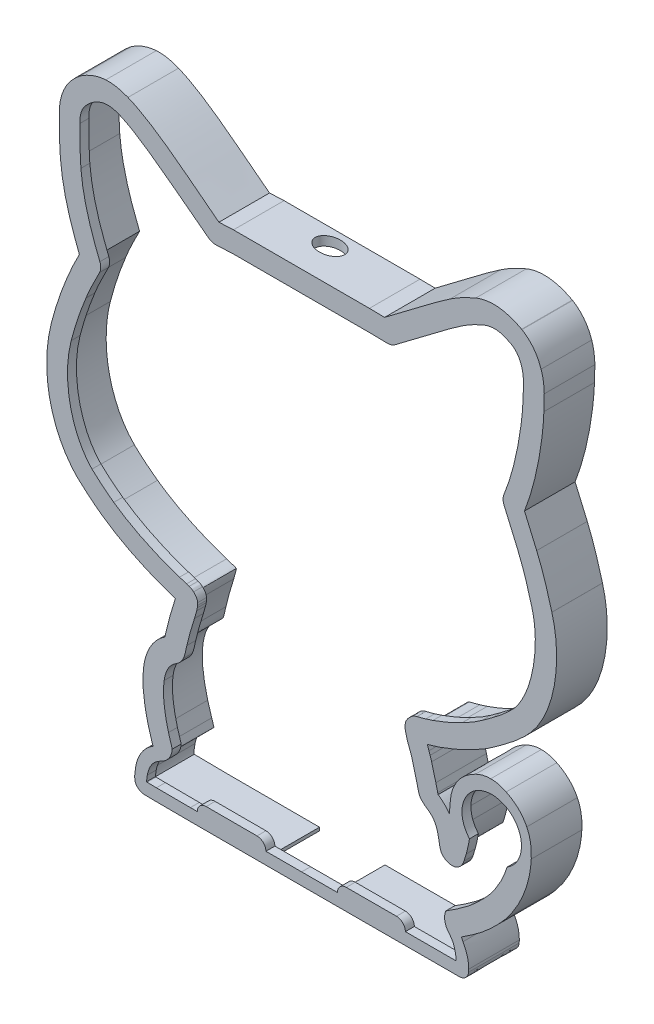
SolidWorks part; units mm, degrees
ref_plane "Front" through (0, 0, 0) normal (0, 0, 1) x (1, 0, 0)
ref_plane "Top" through (0, 0, 0) normal (0, 1, 0) x (1, 0, 0)
ref_plane "Right" through (0, 0, 0) normal (1, 0, 0) x (0, 0, -1)
sketch "Mech_Outlines_Dog" plane through (0, 0, 0) normal (0, 0, 1) x (1, 0, 0)
  line L1 (74.9398, 0.9126) -> (48.9706, 0.8869)
  line L7 (71.492, 32.5287) -> (70.2527, 32.1324)
  line L14 (63.42, 86.4697) -> (60.3508, 86.5232)
  line L15 (60.3508, 86.5232) -> (48.9353, 86.5232)
  line L16 (48.9353, 86.5232) -> (37.5273, 86.5232)
  line L17 (37.5273, 86.5232) -> (34.5339, 86.3884)
  line L22 (73.1431, 2.4109) -> (48.9672, 2.3716)
  line L27 (71.0247, 33.949) -> (69.8274, 33.5656)
  line L32 (63.3944, 84.986) -> (60.338, 85.0395)
  line L33 (60.338, 85.0395) -> (48.9354, 85.0395)
  line L34 (48.9354, 85.0395) -> (37.5613, 85.0395)
  line L35 (37.5613, 85.0395) -> (34.6011, 84.9061)
  line L40 (75.4762, -1.1182) -> (49.0458, -1.1447)
  line L42 (77.0346, 0.7654) -> (77.0108, 0.3114)
  line L48 (60.3548, 88.5576) -> (62.8985, 88.5136)
  line L51 (37.5165, 88.5576) -> (60.3548, 88.5576)
  line L53 (35.0717, 88.4472) -> (37.5165, 88.5576)
  line L56 (34.5113, 86.8831) -> (37.5166, 87.0182)
  line L57 (37.5166, 87.0182) -> (48.9356, 87.0182)
  line L58 (48.9356, 87.0182) -> (60.3546, 87.0182)
  line L59 (60.3546, 87.0182) -> (63.4286, 86.965)
  line L62 (70.4053, 31.6632) -> (71.6522, 32.0554)
  line L63 (75.4324, 0.8747) -> (75.3997, 0.419)
  line L64 (75.3997, 0.419) -> (48.9694, 0.3927)
  spline S0 degree 3 poles (16.1085, 97.6224) (15.1263, 97.5645) (14.0794, 97.2279) (12.9032, 96.4251) knots 0 0 0 0 1 1 1 1
  spline S1 degree 3 poles (12.9032, 96.4251) (10.8702, 94.8674) (10.2573, 93.2137) (10.2274, 91.1494) knots 0 0 0 0 1 1 1 1
  spline S2 degree 3 poles (10.2274, 91.1494) (10.1937, 88.8245) (10.2902, 85.9514) (10.4089, 84.5626) knots 0 0 0 0 1 1 1 1
  spline S3 degree 3 poles (10.4089, 84.5626) (10.8046, 79.9338) (12.2076, 75.8345) (13.7003, 72.1489) knots 0 0 0 0 1 1 1 1
  spline S4 degree 3 poles (13.7003, 72.1489) (13.7533, 72.018) (13.7479, 71.8706) (13.6854, 71.744) knots 0 0 0 0 1 1 1 1
  spline S5 degree 3 poles (13.6854, 71.744) (12.8695, 70.0922) (12.0156, 68.4848) (11.3692, 66.8103) knots 0 0 0 0 1 1 1 1
  spline S6 degree 3 poles (11.3692, 66.8103) (11.3675, 66.8062) (11.3657, 66.8022) (11.3638, 66.7981) knots 0 0 0 0 1 1 1 1
  spline S7 degree 3 poles (11.3638, 66.7981) (10.3632, 64.3951) (9.5104, 61.8412) (8.8174, 59.1813) knots 0 0 0 0 1 1 1 1
  spline S8 degree 3 poles (8.8174, 59.1813) (7.136, 52.6817) (8.6138, 44.9032) (12.7203, 40.814) knots 0 0 0 0 1 1 1 1
  spline S9 degree 3 poles (12.7203, 40.814) (13.8839, 39.7054) (15.1708, 38.6412) (16.5528, 37.6527) knots 0 0 0 0 1 1 1 1
  spline S10 degree 3 poles (16.5528, 37.6527) (19.588, 35.4818) (23.8433, 33.4143) (28.0129, 32.0933) knots 0 0 0 0 1 1 1 1
  spline S11 degree 3 poles (28.0129, 32.0933) (28.4457, 31.9562) (28.8478, 31.8228) (29.152, 31.7174) knots 0 0 0 0 1 1 1 1
  spline S12 degree 3 poles (29.152, 31.7174) (29.3041, 31.6647) (29.4314, 31.6193) (29.5293, 31.582) knots 0 0 0 0 1 1 1 1
  spline S13 degree 3 poles (29.5293, 31.582) (29.6997, 31.528) (29.7592, 31.4685) (29.8367, 31.4215) knots 0 0 0 0 1 1 1 1
  spline S14 degree 3 poles (29.8367, 31.4215) (30.0145, 31.2642) (29.9977, 31.1577) (30.0053, 31.0998) knots 0 0 0 0 1 1 1 1
  spline S15 degree 3 poles (30.0053, 31.0998) (30.013, 31.0418) (30.011, 31.008) (30.0094, 30.9765) knots 0 0 0 0 1 1 1 1
  spline S16 degree 3 poles (30.0094, 30.9765) (30.0062, 30.9135) (29.9984, 30.8639) (29.9884, 30.8065) knots 0 0 0 0 1 1 1 1
  spline S17 degree 3 poles (29.9884, 30.8065) (29.9685, 30.6918) (29.938, 30.5555) (29.897, 30.3921) knots 0 0 0 0 1 1 1 1
  spline S18 degree 3 poles (29.897, 30.3921) (29.815, 30.0653) (29.6927, 29.6377) (29.5475, 29.1758) knots 0 0 0 0 1 1 1 1
  spline S19 degree 3 poles (29.5475, 29.1758) (28.8677, 27.0124) (28.5655, 25.9343) (28.2351, 24.4934) knots 0 0 0 0 1 1 1 1
  spline S20 degree 3 poles (28.2351, 24.4934) (27.9956, 23.449) (27.9088, 22.9752) (27.7373, 22.5937) knots 0 0 0 0 1 1 1 1
  spline S21 degree 3 poles (27.7373, 22.5937) (27.6515, 22.403) (27.5225, 22.233) (27.3845, 22.1142) knots 0 0 0 0 1 1 1 1
  spline S22 degree 3 poles (27.3845, 22.1142) (27.2464, 21.9955) (27.1173, 21.9196) (26.9591, 21.8122) knots 0 0 0 0 1 1 1 1
  spline S23 degree 3 poles (26.9591, 21.8122) (25.5697, 20.8686) (24.7237, 19.4316) (24.4067, 17.4) knots 0 0 0 0 1 1 1 1
  spline S24 degree 3 poles (24.4067, 17.4) (24.0896, 15.3685) (24.3311, 12.7525) (25.1692, 9.5949) knots 0 0 0 0 1 1 1 1
  spline S25 degree 3 poles (25.1692, 9.5949) (25.3317, 8.9826) (25.6352, 7.9761) (25.8316, 7.3959) knots 0 0 0 0 1 1 1 1
  spline S26 degree 3 poles (25.8316, 7.3959) (25.9342, 7.0925) (26.0276, 6.8033) (26.0964, 6.5765) knots 0 0 0 0 1 1 1 1
  spline S27 degree 3 poles (26.0964, 6.5765) (26.1307, 6.4631) (26.1585, 6.3654) (26.1797, 6.2859) knots 0 0 0 0 1 1 1 1
  spline S28 degree 3 poles (26.1797, 6.2859) (26.1902, 6.2462) (26.1992, 6.2118) (26.2067, 6.1769) knots 0 0 0 0 1 1 1 1
  spline S29 degree 3 poles (26.2067, 6.1769) (26.2143, 6.142) (26.2257, 6.1318) (26.2257, 6.0245) knots 0 0 0 0 1 1 1 1
  spline S30 degree 3 poles (26.2257, 6.0245) (26.2257, 5.8348) (26.1568, 5.7565) (26.1167, 5.7015) knots 0 0 0 0 1 1 1 1
  spline S31 degree 3 poles (26.1167, 5.7015) (26.0766, 5.6465) (26.0428, 5.6144) (26.0097, 5.5843) knots 0 0 0 0 1 1 1 1
  spline S32 degree 3 poles (26.0097, 5.5843) (25.9433, 5.5242) (25.878, 5.4775) (25.8031, 5.4286) knots 0 0 0 0 1 1 1 1
  spline S33 degree 3 poles (25.8031, 5.4286) (25.6534, 5.3307) (25.4697, 5.2302) (25.2654, 5.1346) knots 0 0 0 0 1 1 1 1
  spline S34 degree 3 poles (25.2654, 5.1346) (24.0959, 4.5874) (23.3401, 3.5522) (23.0427, 1.9977) knots 0 0 0 0 1 1 1 1
  spline S35 degree 3 poles (23.0427, 1.9977) (22.964, 1.5861) (22.9165, 1.2157) (22.8985, 0.9548) knots 0 0 0 0 1 1 1 1
  spline S36 degree 3 poles (22.8985, 0.9548) (22.8982, 0.9505) (22.8987, 0.9495) (22.8985, 0.9453) knots 0 0 0 0 1 1 1 1
  spline S37 degree 3 poles (22.8985, 0.9453) (22.9412, 0.9442) (22.9602, 0.9428) (23.0095, 0.9418) knots 0 0 0 0 1 1 1 1
  spline S38 degree 3 poles (23.0095, 0.9418) (23.3672, 0.9341) (23.895, 0.9269) (24.5719, 0.9208) knots 0 0 0 0 1 1 1 1
  spline S39 degree 3 poles (24.5719, 0.9208) (25.9256, 0.9085) (27.8776, 0.8993) (30.281, 0.893) knots 0 0 0 0 1 1 1 1
  spline S40 degree 3 poles (30.281, 0.893) (35.0878, 0.8804) (41.7026, 0.8797) (48.9706, 0.8869) knots 0 0 0 0 1 1 1 1
  spline S41 degree 3 poles (74.9398, 0.9126) (74.9724, 1.3839) (74.669, 2.8108) (74.3757, 3.392) knots 0 0 0 0 1 1 1 1
  spline S42 degree 3 poles (74.3757, 3.392) (74.2334, 3.6739) (73.9, 4.1595) (73.7316, 4.3421) knots 0 0 0 0 1 1 1 1
  spline S43 degree 3 poles (73.7316, 4.3421) (73.6085, 4.4757) (73.4981, 4.6071) (73.4106, 4.7234) knots 0 0 0 0 1 1 1 1
  spline S44 degree 3 poles (73.4106, 4.7234) (73.3669, 4.7816) (73.329, 4.8348) (73.2941, 4.8927) knots 0 0 0 0 1 1 1 1
  spline S45 degree 3 poles (73.2941, 4.8927) (73.2767, 4.9217) (73.2598, 4.9511) (73.2413, 4.993) knots 0 0 0 0 1 1 1 1
  spline S46 degree 3 poles (73.2413, 4.993) (73.2228, 5.0349) (73.1905, 5.076) (73.1905, 5.2219) knots 0 0 0 0 1 1 1 1
  spline S47 degree 3 poles (73.1905, 5.2219) (73.1905, 5.5363) (73.3056, 5.5597) (73.3578, 5.616) knots 0 0 0 0 1 1 1 1
  spline S48 degree 3 poles (73.3578, 5.616) (73.41, 5.6724) (73.4583, 5.7124) (73.5122, 5.7542) knots 0 0 0 0 1 1 1 1
  spline S49 degree 3 poles (73.5122, 5.7542) (73.6199, 5.8378) (73.7464, 5.9196) (73.8881, 5.998) knots 0 0 0 0 1 1 1 1
  spline S50 degree 3 poles (73.8881, 5.998) (74.7385, 6.4683) (76.9394, 7.9781) (77.9813, 8.8146) knots 0 0 0 0 1 1 1 1
  spline S51 degree 3 poles (77.9813, 8.8146) (79.226, 9.8139) (80.8168, 11.3707) (81.637, 12.3836) knots 0 0 0 0 1 1 1 1
  spline S52 degree 3 poles (81.637, 12.3836) (84.0319, 15.3411) (85.3661, 18.6885) (85.5378, 22.1256) knots 0 0 0 0 1 1 1 1
  spline S53 degree 3 poles (85.5378, 22.1256) (85.6136, 23.643) (85.4812, 24.4092) (84.9811, 25.4434) knots 0 0 0 0 1 1 1 1
  spline S54 degree 3 poles (84.9811, 25.4434) (84.4438, 26.5544) (83.7351, 27.2385) (82.4747, 27.8394) knots 0 0 0 0 1 1 1 1
  spline S55 degree 3 poles (82.4747, 27.8394) (81.5208, 28.2943) (81.637, 28.2688) (80.7593, 28.2688) knots 0 0 0 0 1 1 1 1
  spline S56 degree 3 poles (80.7593, 28.2688) (79.8855, 28.2688) (79.9954, 28.293) (79.0797, 27.8543) knots 0 0 0 0 1 1 1 1
  spline S57 degree 3 poles (79.0797, 27.8543) (77.5705, 27.1313) (76.7543, 26.2458) (76.259, 24.8217) knots 0 0 0 0 1 1 1 1
  spline S58 degree 3 poles (76.259, 24.8217) (76.0847, 24.3204) (76.007, 23.8462) (75.938, 22.7575) knots 0 0 0 0 1 1 1 1
  spline S59 degree 3 poles (75.938, 22.7575) (75.8864, 21.9425) (75.7936, 20.8688) (75.7267, 20.3289) knots 0 0 0 0 1 1 1 1
  spline S60 degree 3 poles (75.7267, 20.3289) (75.6352, 19.5905) (75.4028, 18.5493) (75.1701, 17.6863) knots 0 0 0 0 1 1 1 1
  spline S61 degree 3 poles (75.1701, 17.6863) (75.0537, 17.2549) (74.9391, 16.8726) (74.8348, 16.5885) knots 0 0 0 0 1 1 1 1
  spline S62 degree 3 poles (74.8348, 16.5885) (74.7827, 16.4465) (74.7375, 16.3338) (74.6736, 16.2215) knots 0 0 0 0 1 1 1 1
  spline S63 degree 3 poles (74.6736, 16.2215) (74.6417, 16.1654) (74.6178, 16.1084) (74.5125, 16.0204) knots 0 0 0 0 1 1 1 1
  spline S64 degree 3 poles (74.5125, 16.0204) (74.4598, 15.9763) (74.3749, 15.9137) (74.226, 15.8984) knots 0 0 0 0 1 1 1 1
  spline S65 degree 3 poles (74.226, 15.8984) (74.0771, 15.8832) (73.8945, 15.9611) (73.8088, 16.0468) knots 0 0 0 0 1 1 1 1
  spline S66 degree 3 poles (73.8088, 16.0468) (73.6952, 16.1604) (73.7087, 16.1881) (73.6971, 16.2161) knots 0 0 0 0 1 1 1 1
  spline S67 degree 3 poles (73.6971, 16.2161) (73.6855, 16.244) (73.6793, 16.2621) (73.674, 16.2791) knots 0 0 0 0 1 1 1 1
  spline S68 degree 3 poles (73.674, 16.2791) (73.6635, 16.313) (73.6564, 16.3423) (73.6483, 16.3759) knots 0 0 0 0 1 1 1 1
  spline S69 degree 3 poles (73.6483, 16.3759) (73.6321, 16.4431) (73.6147, 16.5243) (73.5955, 16.6217) knots 0 0 0 0 1 1 1 1
  spline S70 degree 3 poles (73.5955, 16.6217) (73.5571, 16.8166) (73.512, 17.0723) (73.4675, 17.3484) knots 0 0 0 0 1 1 1 1
  spline S71 degree 3 poles (73.4675, 17.3484) (73.116, 19.5286) (72.2864, 20.9205) (70.8513, 21.8493) knots 0 0 0 0 1 1 1 1
  spline S72 degree 3 poles (70.8513, 21.8493) (70.681, 21.9596) (70.5241, 22.0799) (70.3929, 22.1988) knots 0 0 0 0 1 1 1 1
  spline S73 degree 3 poles (70.3929, 22.1988) (70.3273, 22.2582) (70.2681, 22.3165) (70.2134, 22.3816) knots 0 0 0 0 1 1 1 1
  spline S74 degree 3 poles (70.2134, 22.3816) (70.1586, 22.4467) (70.1012, 22.4987) (70.0536, 22.662) knots 0 0 0 0 1 1 1 1
  spline S75 degree 3 poles (70.0536, 22.662) (70.022, 22.77) (69.9713, 22.98) (69.8836, 23.3358) knots 0 0 0 0 1 1 1 1
  spline S76 degree 3 poles (69.8836, 23.3358) (69.7959, 23.6916) (69.6827, 24.1554) (69.5653, 24.6422) knots 0 0 0 0 1 1 1 1
  spline S77 degree 3 poles (69.5653, 24.6422) (69.3325, 25.607) (69.0226, 26.7879) (68.8928, 27.2143) knots 0 0 0 0 1 1 1 1
  spline S78 degree 3 poles (68.8928, 27.2143) (68.829, 27.4238) (68.7314, 27.6944) (68.6449, 27.943) knots 0 0 0 0 1 1 1 1
  spline S79 degree 3 poles (68.6449, 27.943) (68.4728, 28.6982) (68.1277, 29.2538) (67.902, 30.1603) knots 0 0 0 0 1 1 1 1
  spline S80 degree 3 poles (67.902, 30.1603) (67.8356, 30.4354) (67.788, 30.6996) (67.8519, 30.9947) knots 0 0 0 0 1 1 1 1
  spline S81 degree 3 poles (67.8519, 30.9947) (67.9158, 31.2897) (68.2169, 31.6162) (68.5562, 31.6746) knots 0 0 0 0 1 1 1 1
  spline S82 degree 3 poles (68.5562, 31.6746) (68.7453, 31.7047) (69.5821, 31.9215) (70.2527, 32.1324) knots 0 0 0 0 1 1 1 1
  spline S83 degree 3 poles (71.492, 32.5287) (73.2584, 33.1478) (74.9712, 33.8823) (76.6363, 34.7642) knots 0 0 0 0 1 1 1 1
  spline S84 degree 3 poles (76.6363, 34.7642) (76.639, 34.7656) (76.6421, 34.767) (76.6451, 34.7683) knots 0 0 0 0 1 1 1 1
  spline S85 degree 3 poles (76.6451, 34.7683) (78.05, 35.4763) (79.1164, 36.1165) (80.1477, 36.8684) knots 0 0 0 0 1 1 1 1
  spline S86 degree 3 poles (80.1477, 36.8684) (80.5017, 37.1265) (81.2678, 37.6841) (81.8523, 38.1077) knots 0 0 0 0 1 1 1 1
  spline S87 degree 3 poles (81.8523, 38.1077) (82.9542, 38.9064) (84.0321, 39.8115) (85.0441, 40.7815) knots 0 0 0 0 1 1 1 1
  spline S88 degree 3 poles (85.0441, 40.7815) (89.4404, 44.9023) (90.6758, 53.4557) (89.0723, 59.1176) knots 0 0 0 0 1 1 1 1
  spline S89 degree 3 poles (89.0723, 59.1176) (89.0713, 59.121) (89.0706, 59.1243) (89.0695, 59.1277) knots 0 0 0 0 1 1 1 1
  spline S90 degree 3 poles (89.0695, 59.1277) (88.3821, 61.7674) (87.5422, 64.3151) (86.5996, 66.5786) knots 0 0 0 0 1 1 1 1
  spline S91 degree 3 poles (86.5996, 66.5786) (85.9445, 68.1619) (85.0951, 70.1031) (84.3316, 71.8319) knots 0 0 0 0 1 1 1 1
  spline S92 degree 3 poles (84.3316, 71.8319) (84.277, 71.9552) (84.2751, 72.0953) (84.3262, 72.22) knots 0 0 0 0 1 1 1 1
  spline S93 degree 3 poles (84.3262, 72.22) (86.2256, 76.8323) (87.4523, 83.2033) (87.6568, 88.2549) knots 0 0 0 0 1 1 1 1
  spline S94 degree 3 poles (87.6568, 88.2549) (87.6933, 89.156) (87.7129, 90.0068) (87.7164, 90.806) knots 0 0 0 0 1 1 1 1
  spline S95 degree 3 poles (87.7164, 90.806) (87.7165, 91.2801) (87.6649, 92.3563) (87.2904, 93.4831) knots 0 0 0 0 1 1 1 1
  spline S96 degree 3 poles (87.2904, 93.4831) (86.9162, 94.609) (86.2349, 95.7695) (84.9729, 96.5191) knots 0 0 0 0 1 1 1 1
  spline S97 degree 3 poles (84.9729, 96.5191) (83.6571, 97.2286) (81.5853, 98.1604) (79.0153, 97.1117) knots 0 0 0 0 1 1 1 1
  spline S98 degree 3 poles (79.0153, 97.1117) (77.7563, 96.598) (76.3931, 95.8948) (75.0467, 94.9927) knots 0 0 0 0 1 1 1 1
  spline S99 degree 3 poles (75.0467, 94.9927) (71.9886, 92.9435) (67.928, 89.6189) (63.7193, 86.5645) knots 0 0 0 0 1 1 1 1
  spline S100 degree 3 poles (63.7193, 86.5645) (63.6325, 86.5012) (63.5274, 86.4679) (63.42, 86.4697) knots 0 0 0 0 1 1 1 1
  spline S101 degree 3 poles (34.5339, 86.3884) (34.4203, 86.3833) (34.3084, 86.4175) (34.217, 86.4853) knots 0 0 0 0 1 1 1 1
  spline S102 degree 3 poles (34.217, 86.4853) (29.3204, 90.1096) (23.1108, 95.3799) (18.9569, 97.08) knots 0 0 0 0 1 1 1 1
  spline S103 degree 3 poles (18.9569, 97.08) (18.0268, 97.4561) (17.0933, 97.6805) (16.1085, 97.6224) knots 0 0 0 0 1 1 1 1
  spline S104 degree 3 poles (16.1938, 96.1413) (15.4989, 96.1004) (14.7441, 95.8759) (13.7687, 95.2169) knots 0 0 0 0 1 1 1 1
  spline S105 degree 3 poles (13.7687, 95.2169) (12.0783, 93.9098) (11.7344, 92.871) (11.7092, 91.1291) knots 0 0 0 0 1 1 1 1
  spline S106 degree 3 poles (11.7092, 91.1291) (11.6763, 88.8622) (11.776, 85.976) (11.8859, 84.69) knots 0 0 0 0 1 1 1 1
  spline S107 degree 3 poles (11.8859, 84.69) (12.2626, 80.2837) (13.6038, 76.3379) (15.0744, 72.707) knots 0 0 0 0 1 1 1 1
  spline S108 degree 3 poles (15.0744, 72.707) (15.2863, 72.1834) (15.2643, 71.5942) (15.0141, 71.0877) knots 0 0 0 0 1 1 1 1
  spline S109 degree 3 poles (15.0141, 71.0877) (14.185, 69.4091) (13.3549, 67.84) (12.7515, 66.2767) knots 0 0 0 0 1 1 1 1
  spline S110 degree 3 poles (12.7515, 66.2767) (12.7453, 66.2605) (12.739, 66.2445) (12.7325, 66.2286) knots 0 0 0 0 1 1 1 1
  spline S111 degree 3 poles (12.7325, 66.2286) (11.7606, 63.8947) (10.9288, 61.4063) (10.2525, 58.8108) knots 0 0 0 0 1 1 1 1
  spline S112 degree 3 poles (10.2525, 58.8108) (8.6952, 52.7918) (10.1873, 45.4432) (13.7558, 41.878) knots 0 0 0 0 1 1 1 1
  spline S113 degree 3 poles (13.7558, 41.878) (14.8637, 40.8235) (16.0922, 39.8065) (17.4142, 38.8609) knots 0 0 0 0 1 1 1 1
  spline S114 degree 3 poles (17.4142, 38.8609) (20.2797, 36.8114) (24.4364, 34.7832) (28.4592, 33.5087) knots 0 0 0 0 1 1 1 1
  spline S115 degree 3 poles (28.4592, 33.5087) (28.903, 33.3681) (29.3143, 33.2323) (29.6362, 33.1207) knots 0 0 0 0 1 1 1 1
  spline S116 degree 3 poles (29.6362, 33.1207) (29.7972, 33.0649) (29.9337, 33.016) (30.0568, 32.969) knots 0 0 0 0 1 1 1 1
  spline S117 degree 3 poles (30.0568, 32.969) (30.6405, 32.7016) (30.339, 32.9545) (30.818, 32.5342) knots 0 0 0 0 1 1 1 1
  spline S118 degree 3 poles (30.818, 32.5342) (31.5202, 31.9131) (31.4475, 31.5028) (31.4749, 31.2955) knots 0 0 0 0 1 1 1 1
  spline S119 degree 3 poles (31.4749, 31.2955) (31.5024, 31.0883) (31.4942, 30.9868) (31.4898, 30.9014) knots 0 0 0 0 1 1 1 1
  spline S120 degree 3 poles (31.4898, 30.9014) (31.4811, 30.7305) (31.4648, 30.6433) (31.4492, 30.5533) knots 0 0 0 0 1 1 1 1
  spline S121 degree 3 poles (31.4492, 30.5533) (31.4179, 30.3732) (31.3803, 30.2159) (31.3341, 30.0318) knots 0 0 0 0 1 1 1 1
  spline S122 degree 3 poles (31.3341, 30.0318) (31.2416, 29.6635) (31.1141, 29.2167) (30.9616, 28.7315) knots 0 0 0 0 1 1 1 1
  spline S123 degree 3 poles (30.9616, 28.7315) (30.2864, 26.583) (30.002, 25.5679) (29.6796, 24.1622) knots 0 0 0 0 1 1 1 1
  spline S124 degree 3 poles (29.6796, 24.1622) (29.4419, 23.1257) (29.4009, 22.6792) (29.0891, 21.9856) knots 0 0 0 0 1 1 1 1
  spline S125 degree 3 poles (29.0891, 21.9856) (28.9331, 21.6388) (28.6202, 21.2223) (28.3502, 20.9901) knots 0 0 0 0 1 1 1 1
  spline S126 degree 3 poles (28.3502, 20.9901) (28.0802, 20.7578) (27.9259, 20.6757) (27.7915, 20.5844) knots 0 0 0 0 1 1 1 1
  spline S127 degree 3 poles (27.7915, 20.5844) (26.7593, 19.8835) (26.1415, 18.9015) (25.8715, 17.1718) knots 0 0 0 0 1 1 1 1
  spline S128 degree 3 poles (25.8715, 17.1718) (25.6015, 15.4421) (25.7971, 13.0078) (26.6016, 9.9769) knots 0 0 0 0 1 1 1 1
  spline S129 degree 3 poles (26.6016, 9.9769) (26.7505, 9.4157) (27.0568, 8.4004) (27.2355, 7.8727) knots 0 0 0 0 1 1 1 1
  spline S130 degree 3 poles (27.2355, 7.8727) (27.3428, 7.5557) (27.4394, 7.2555) (27.5145, 7.0079) knots 0 0 0 0 1 1 1 1
  spline S131 degree 3 poles (27.5145, 7.0079) (27.552, 6.8841) (27.5835, 6.7751) (27.612, 6.6679) knots 0 0 0 0 1 1 1 1
  spline S132 degree 3 poles (27.612, 6.6679) (27.6262, 6.6143) (27.6399, 6.5627) (27.6553, 6.4912) knots 0 0 0 0 1 1 1 1
  spline S133 degree 3 poles (27.6553, 6.4912) (27.6708, 6.4196) (27.7075, 6.4282) (27.7075, 6.0252) knots 0 0 0 0 1 1 1 1
  spline S134 degree 3 poles (27.7075, 6.0252) (27.7075, 5.2923) (27.4472, 5.0106) (27.314, 4.8279) knots 0 0 0 0 1 1 1 1
  spline S135 degree 3 poles (27.314, 4.8279) (27.1808, 4.6452) (27.0851, 4.5581) (27.0038, 4.4845) knots 0 0 0 0 1 1 1 1
  spline S136 degree 3 poles (27.0038, 4.4845) (26.8414, 4.3374) (26.7289, 4.2629) (26.6131, 4.1872) knots 0 0 0 0 1 1 1 1
  spline S137 degree 3 poles (26.6131, 4.1872) (26.3815, 4.0358) (26.1526, 3.9128) (25.8925, 3.791) knots 0 0 0 0 1 1 1 1
  spline S138 degree 3 poles (25.8925, 3.791) (25.3519, 3.538) (25.011, 3.0738) (24.7561, 2.4054) knots 0 0 0 0 1 1 1 1
  spline S139 degree 3 poles (24.7561, 2.4054) (26.098, 2.3937) (27.954, 2.3844) (30.283, 2.3783) knots 0 0 0 0 1 1 1 1
  spline S140 degree 3 poles (30.283, 2.3783) (35.0865, 2.3658) (41.7003, 2.3644) (48.9672, 2.3716) knots 0 0 0 0 1 1 1 1
  spline S141 degree 3 poles (73.1431, 2.4109) (73.1124, 2.5325) (73.0842, 2.6997) (73.0645, 2.7386) knots 0 0 0 0 1 1 1 1
  spline S142 degree 3 poles (73.0645, 2.7386) (72.8449, 3.1433) (72.4981, 3.5205) (72.2383, 3.8473) knots 0 0 0 0 1 1 1 1
  spline S143 degree 3 poles (72.2383, 3.8473) (72.1747, 3.9319) (72.1144, 4.0144) (72.0372, 4.1425) knots 0 0 0 0 1 1 1 1
  spline S144 degree 3 poles (72.0372, 4.1425) (71.9985, 4.2066) (71.9552, 4.279) (71.8977, 4.4094) knots 0 0 0 0 1 1 1 1
  spline S145 degree 3 poles (71.8977, 4.4094) (71.8401, 4.5398) (71.7209, 4.6745) (71.7209, 5.2376) knots 0 0 0 0 1 1 1 1
  spline S146 degree 3 poles (71.7209, 5.2376) (71.7209, 6.4544) (72.1416, 6.4876) (72.283, 6.6402) knots 0 0 0 0 1 1 1 1
  spline S147 degree 3 poles (72.283, 6.6402) (72.4244, 6.7928) (72.5209, 6.869) (72.6162, 6.9429) knots 0 0 0 0 1 1 1 1
  spline S148 degree 3 poles (72.6162, 6.9429) (72.8068, 7.0908) (72.9824, 7.201) (73.1844, 7.3127) knots 0 0 0 0 1 1 1 1
  spline S149 degree 3 poles (73.1844, 7.3127) (73.8246, 7.6667) (76.1327, 9.2382) (77.0663, 9.9878) knots 0 0 0 0 1 1 1 1
  spline S150 degree 3 poles (77.0663, 9.9878) (78.2095, 10.9055) (79.7957, 12.4662) (80.4979, 13.3333) knots 0 0 0 0 1 1 1 1
  spline S151 degree 3 poles (80.4979, 13.3333) (82.7172, 16.074) (83.9146, 19.1142) (84.0696, 22.2159) knots 0 0 0 0 1 1 1 1
  spline S152 degree 3 poles (84.0696, 22.2159) (84.1391, 23.608) (84.0692, 23.9653) (83.6592, 24.8131) knots 0 0 0 0 1 1 1 1
  spline S153 degree 3 poles (83.6592, 24.8131) (83.2508, 25.6575) (82.8926, 26.0183) (81.8496, 26.5156) knots 0 0 0 0 1 1 1 1
  spline S154 degree 3 poles (81.8496, 26.5156) (81.404, 26.7167) (81.6277, 26.8014) (80.7735, 26.8014) knots 0 0 0 0 1 1 1 1
  spline S155 degree 3 poles (80.7735, 26.8014) (79.9242, 26.8014) (80.2197, 26.7515) (79.7353, 26.5326) knots 0 0 0 0 1 1 1 1
  spline S156 degree 3 poles (79.7353, 26.5326) (78.4713, 25.9612) (78.0585, 25.4528) (77.6751, 24.3505) knots 0 0 0 0 1 1 1 1
  spline S157 degree 3 poles (77.6751, 24.3505) (77.5544, 24.0033) (77.4994, 23.7229) (77.4334, 22.6798) knots 0 0 0 0 1 1 1 1
  spline S158 degree 3 poles (77.4334, 22.6798) (77.3798, 21.8337) (77.2901, 20.778) (77.214, 20.1632) knots 0 0 0 0 1 1 1 1
  spline S159 degree 3 poles (77.214, 20.1632) (77.105, 19.2836) (76.865, 18.2328) (76.618, 17.3168) knots 0 0 0 0 1 1 1 1
  spline S160 degree 3 poles (76.618, 17.3168) (76.4945, 16.8587) (76.374, 16.4531) (76.2421, 16.0937) knots 0 0 0 0 1 1 1 1
  spline S161 degree 3 poles (76.2421, 16.0937) (76.1762, 15.914) (76.1262, 15.7639) (75.9787, 15.5045) knots 0 0 0 0 1 1 1 1
  spline S162 degree 3 poles (75.9787, 15.5045) (75.9049, 15.3748) (75.8576, 15.2148) (75.4789, 14.8984) knots 0 0 0 0 1 1 1 1
  spline S163 degree 3 poles (75.4789, 14.8984) (75.2895, 14.7402) (74.9692, 14.4978) (74.3919, 14.4385) knots 0 0 0 0 1 1 1 1
  spline S164 degree 3 poles (74.3919, 14.4385) (73.8146, 14.3792) (73.1017, 14.6865) (72.774, 15.0142) knots 0 0 0 0 1 1 1 1
  spline S165 degree 3 poles (72.774, 15.0142) (72.324, 15.4641) (72.381, 15.5658) (72.3406, 15.663) knots 0 0 0 0 1 1 1 1
  spline S166 degree 3 poles (72.3406, 15.663) (72.3001, 15.7602) (72.2851, 15.8107) (72.2715, 15.8546) knots 0 0 0 0 1 1 1 1
  spline S167 degree 3 poles (72.2715, 15.8546) (72.2442, 15.9424) (72.2318, 15.9928) (72.2194, 16.0443) knots 0 0 0 0 1 1 1 1
  spline S168 degree 3 poles (72.2194, 16.0443) (72.1945, 16.1472) (72.1753, 16.2414) (72.1537, 16.351) knots 0 0 0 0 1 1 1 1
  spline S169 degree 3 poles (72.1537, 16.351) (72.1104, 16.5703) (72.0631, 16.8376) (72.0162, 17.1285) knots 0 0 0 0 1 1 1 1
  spline S170 degree 3 poles (72.0162, 17.1285) (71.7093, 19.0315) (71.1304, 19.9262) (70.059, 20.6196) knots 0 0 0 0 1 1 1 1
  spline S171 degree 3 poles (70.059, 20.6196) (69.8204, 20.7741) (69.6132, 20.9315) (69.4102, 21.1154) knots 0 0 0 0 1 1 1 1
  spline S172 degree 3 poles (69.4102, 21.1154) (69.3087, 21.2073) (69.2094, 21.3029) (69.0919, 21.4425) knots 0 0 0 0 1 1 1 1
  spline S173 degree 3 poles (69.0919, 21.4425) (68.9745, 21.582) (68.8106, 21.6882) (68.6429, 22.2626) knots 0 0 0 0 1 1 1 1
  spline S174 degree 3 poles (68.6429, 22.2626) (68.5625, 22.538) (68.545, 22.6375) (68.4566, 22.9961) knots 0 0 0 0 1 1 1 1
  spline S175 degree 3 poles (68.4566, 22.9961) (68.3682, 23.355) (68.2543, 23.8209) (68.1363, 24.3099) knots 0 0 0 0 1 1 1 1
  spline S176 degree 3 poles (68.1363, 24.3099) (67.9088, 25.2527) (67.5877, 26.4666) (67.4868, 26.798) knots 0 0 0 0 1 1 1 1
  spline S177 degree 3 poles (67.4868, 26.798) (67.441, 26.9485) (67.3481, 27.21) (67.2573, 27.4712) knots 0 0 0 0 1 1 1 1
  spline S178 degree 3 poles (67.2573, 27.4712) (66.9209, 28.4482) (66.9, 28.1075) (66.4737, 29.828) knots 0 0 0 0 1 1 1 1
  spline S179 degree 3 poles (66.4737, 29.828) (66.3826, 30.2052) (66.2637, 30.623) (66.4155, 31.324) knots 0 0 0 0 1 1 1 1
  spline S180 degree 3 poles (66.4155, 31.324) (66.5672, 32.025) (67.4922, 33.0109) (68.3185, 33.1532) knots 0 0 0 0 1 1 1 1
  spline S181 degree 3 poles (68.3185, 33.1532) (68.3268, 33.1546) (68.3352, 33.156) (68.3436, 33.1573) knots 0 0 0 0 1 1 1 1
  spline S182 degree 3 poles (68.3436, 33.1573) (68.2419, 33.1411) (69.2025, 33.3691) (69.8274, 33.5656) knots 0 0 0 0 1 1 1 1
  spline S183 degree 3 poles (71.0247, 33.949) (72.7235, 34.545) (74.3625, 35.248) (75.9529, 36.0904) knots 0 0 0 0 1 1 1 1
  spline S184 degree 3 poles (75.9529, 36.0904) (75.9648, 36.0968) (75.9768, 36.1031) (75.9888, 36.1093) knots 0 0 0 0 1 1 1 1
  spline S185 degree 3 poles (75.9888, 36.1093) (77.3417, 36.7911) (78.3228, 37.3819) (79.2843, 38.0828) knots 0 0 0 0 1 1 1 1
  spline S186 degree 3 poles (79.2843, 38.0828) (79.6409, 38.3428) (80.4071, 38.8996) (80.9929, 39.3242) knots 0 0 0 0 1 1 1 1
  spline S187 degree 3 poles (80.9929, 39.3242) (82.0357, 40.08) (83.0639, 40.9435) (84.029, 41.8685) knots 0 0 0 0 1 1 1 1
  spline S189 degree 3 poles (84.029, 41.8685) (87.797, 45.4005) (89.0902, 53.6089) (87.6433, 58.7174) knots 0 0 0 0 1 1 1 1
  spline S190 degree 3 poles (87.6433, 58.7174) (87.6396, 58.7309) (87.636, 58.7445) (87.6325, 58.7581) knots 0 0 0 0 1 1 1 1
  spline S191 degree 3 poles (87.6325, 58.7581) (86.9607, 61.3378) (86.1393, 63.8249) (85.2284, 66.0126) knots 0 0 0 0 1 1 1 1
  spline S192 degree 3 poles (85.2284, 66.0126) (84.5826, 67.5731) (83.7358, 69.508) (82.9738, 71.2334) knots 0 0 0 0 1 1 1 1
  spline S193 degree 3 poles (82.9738, 71.2334) (82.7558, 71.7269) (82.7487, 72.2881) (82.9542, 72.787) knots 0 0 0 0 1 1 1 1
  spline S194 degree 3 poles (82.9542, 72.787) (84.7571, 77.1647) (85.9768, 83.4515) (86.1738, 88.3159) knots 0 0 0 0 1 1 1 1
  spline S195 degree 3 poles (86.1738, 88.3159) (86.2095, 89.1989) (86.2292, 90.0306) (86.2327, 90.8081) knots 0 0 0 0 1 1 1 1
  spline S196 degree 3 poles (86.2327, 90.8081) (86.2327, 91.1814) (86.181, 92.1145) (85.8819, 93.0146) knots 0 0 0 0 1 1 1 1
  spline S197 degree 3 poles (85.8819, 93.0146) (85.5839, 93.9112) (85.1, 94.7112) (84.2234, 95.2359) knots 0 0 0 0 1 1 1 1
  spline S198 degree 3 poles (84.2234, 95.2359) (83.0241, 95.8803) (81.5688, 96.5501) (79.5762, 95.7371) knots 0 0 0 0 1 1 1 1
  spline S199 degree 3 poles (79.5762, 95.7371) (78.4083, 95.2605) (77.1307, 94.6023) (75.8731, 93.7595) knots 0 0 0 0 1 1 1 1
  spline S200 degree 3 poles (75.8731, 93.7595) (72.9259, 91.7847) (68.8472, 88.4521) (64.591, 85.3632) knots 0 0 0 0 1 1 1 1
  spline S201 degree 3 poles (64.591, 85.3632) (64.2436, 85.111) (63.8236, 84.9786) (63.3944, 84.986) knots 0 0 0 0 1 1 1 1
  spline S202 degree 3 poles (34.6011, 84.9061) (34.1469, 84.8854) (33.6995, 85.0217) (33.334, 85.2921) knots 0 0 0 0 1 1 1 1
  spline S203 degree 3 poles (33.334, 85.2921) (28.3627, 88.9715) (22.0502, 94.2093) (18.3962, 95.7052) knots 0 0 0 0 1 1 1 1
  spline S204 degree 3 poles (18.3962, 95.7052) (17.598, 96.0277) (16.8978, 96.1828) (16.1938, 96.1413) knots 0 0 0 0 1 1 1 1
  spline S205 degree 3 poles (16.0611, 99.6528) (14.6917, 99.572) (13.2477, 99.079) (11.8148, 98.0978) knots 0 0 0 0 1 1 1 1
  spline S206 degree 3 poles (11.8148, 98.0978) (11.7928, 98.0826) (11.7711, 98.0668) (11.7498, 98.0504) knots 0 0 0 0 1 1 1 1
  spline S207 degree 3 poles (11.7498, 98.0504) (9.2878, 96.1693) (8.3016, 93.6701) (8.2655, 91.1792) knots 0 0 0 0 1 1 1 1
  spline S208 degree 3 poles (8.2655, 91.1792) (8.2306, 88.7748) (8.3237, 85.9188) (8.4544, 84.3893) knots 0 0 0 0 1 1 1 1
  spline S209 degree 3 poles (8.4544, 84.3893) (8.8524, 79.7334) (10.2049, 75.652) (11.6354, 72.0447) knots 0 0 0 0 1 1 1 1
  spline S210 degree 3 poles (11.6354, 72.0447) (10.9212, 70.619) (10.1679, 69.1565) (9.5495, 67.5573) knots 0 0 0 0 1 1 1 1
  spline S211 degree 3 poles (9.5495, 67.5573) (8.514, 65.0675) (7.6345, 62.4324) (6.9212, 59.6939) knots 0 0 0 0 1 1 1 1
  spline S212 degree 3 poles (6.9212, 59.6939) (5.0707, 52.5417) (6.5251, 44.1835) (11.3618, 39.3708) knots 0 0 0 0 1 1 1 1
  spline S213 degree 3 poles (11.3618, 39.3708) (11.3694, 39.3631) (11.377, 39.3554) (11.3848, 39.3478) knots 0 0 0 0 1 1 1 1
  spline S214 degree 3 poles (11.3848, 39.3478) (12.6215, 38.169) (13.9827, 37.0447) (15.4421, 36.0009) knots 0 0 0 0 1 1 1 1
  spline S215 degree 3 poles (15.4421, 36.0009) (18.71, 33.6636) (23.1001, 31.5412) (27.4711, 30.1564) knots 0 0 0 0 1 1 1 1
  spline S216 degree 3 poles (27.4711, 30.1564) (27.5813, 30.1215) (27.6534, 30.0955) (27.7583, 30.0616) knots 0 0 0 0 1 1 1 1
  spline S217 degree 3 poles (27.7583, 30.0616) (27.7278, 29.9601) (27.7132, 29.8953) (27.6797, 29.7887) knots 0 0 0 0 1 1 1 1
  spline S218 degree 3 poles (27.6797, 29.7887) (26.9935, 27.605) (26.6668, 26.4399) (26.3252, 24.9505) knots 0 0 0 0 1 1 1 1
  spline S219 degree 3 poles (26.3252, 24.9505) (26.1044, 23.9876) (25.9955, 23.6101) (25.988, 23.5635) knots 0 0 0 0 1 1 1 1
  spline S220 degree 3 poles (25.988, 23.5635) (25.9453, 23.5339) (25.9675, 23.5506) (25.8898, 23.4978) knots 0 0 0 0 1 1 1 1
  spline S221 degree 3 poles (25.8898, 23.4978) (24.0106, 22.2217) (22.8514, 20.1616) (22.4698, 17.7163) knots 0 0 0 0 1 1 1 1
  spline S222 degree 3 poles (22.4698, 17.7163) (22.0881, 15.271) (22.3921, 12.4074) (23.2763, 9.0762) knots 0 0 0 0 1 1 1 1
  spline S223 degree 3 poles (23.2763, 9.0762) (23.4575, 8.3938) (23.7572, 7.3986) (23.978, 6.7465) knots 0 0 0 0 1 1 1 1
  spline S224 degree 3 poles (23.978, 6.7465) (23.987, 6.7197) (23.9921, 6.7018) (24.001, 6.6754) knots 0 0 0 0 1 1 1 1
  spline S225 degree 3 poles (24.001, 6.6754) (22.4988, 5.7713) (21.4695, 4.2232) (21.1173, 2.3824) knots 0 0 0 0 1 1 1 1
  spline S226 degree 3 poles (21.1173, 2.3824) (21.0249, 1.8994) (20.9675, 1.4678) (20.9419, 1.0977) knots 0 0 0 0 1 1 1 1
  spline S227 degree 3 poles (20.9419, 1.0977) (20.9292, 0.9126) (20.9226, 0.7479) (20.9331, 0.5559) knots 0 0 0 0 1 1 1 1
  spline S228 degree 3 poles (20.9331, 0.5559) (20.9384, 0.4599) (20.945, 0.3593) (20.9785, 0.2051) knots 0 0 0 0 1 1 1 1
  spline S229 degree 3 poles (20.9785, 0.2051) (21.012, 0.0508) (20.9807, -0.1756) (21.4173, -0.6123) knots 0 0 0 0 1 1 1 1
  spline S230 degree 3 poles (21.4173, -0.6123) (21.4176, -0.6126) (21.7791, -0.8855) (21.8765, -0.9293) knots 0 0 0 0 1 1 1 1
  spline S231 degree 3 poles (21.8765, -0.9293) (21.9739, -0.9731) (22.0342, -0.9912) (22.0824, -1.0051) knots 0 0 0 0 1 1 1 1
  spline S232 degree 3 poles (22.0824, -1.0051) (22.1788, -1.033) (22.2254, -1.0393) (22.2639, -1.0458) knots 0 0 0 0 1 1 1 1
  spline S233 degree 3 poles (22.2639, -1.0458) (22.3408, -1.0587) (22.3753, -1.0617) (22.4095, -1.0647) knots 0 0 0 0 1 1 1 1
  spline S234 degree 3 poles (22.4095, -1.0647) (22.4778, -1.0709) (22.5274, -1.0729) (22.5869, -1.0756) knots 0 0 0 0 1 1 1 1
  spline S235 degree 3 poles (22.5869, -1.0756) (22.7059, -1.081) (22.8521, -1.0851) (23.0393, -1.0891) knots 0 0 0 0 1 1 1 1
  spline S236 degree 3 poles (23.0393, -1.0891) (23.4137, -1.0972) (23.9456, -1.1046) (24.6267, -1.1108) knots 0 0 0 0 1 1 1 1
  spline S237 degree 3 poles (24.6267, -1.1108) (25.9891, -1.1232) (27.943, -1.1323) (30.3487, -1.1386) knots 0 0 0 0 1 1 1 1
  spline S238 degree 3 poles (30.3487, -1.1386) (35.16, -1.1512) (41.7763, -1.1519) (49.0458, -1.1447) knots 0 0 0 0 1 1 1 1
  spline S239 degree 3 poles (75.4762, -1.1182) (76.2834, -1.1176) (76.953, -0.4937) (77.0108, 0.3114) knots 0 0 0 0 1 1 1 1
  spline S240 degree 3 poles (77.0346, 0.7654) (77.0544, 2.054) (76.6753, 3.1912) (76.0582, 4.2601) knots 0 0 0 0 1 1 1 1
  spline S241 degree 3 poles (76.0582, 4.2601) (75.9987, 4.4666) (75.8808, 4.6452) (75.8052, 4.8394) knots 0 0 0 0 1 1 1 1
  spline S242 degree 3 poles (75.8052, 4.8394) (76.9391, 5.5555) (78.298, 6.4929) (79.2246, 7.2368) knots 0 0 0 0 1 1 1 1
  spline S243 degree 3 poles (79.2246, 7.2368) (80.6087, 8.3479) (82.2065, 9.8993) (83.1884, 11.1119) knots 0 0 0 0 1 1 1 1
  spline S244 degree 3 poles (83.1884, 11.1119) (85.824, 14.3666) (87.3457, 18.1368) (87.5403, 22.0336) knots 0 0 0 0 1 1 1 1
  spline S245 degree 3 poles (87.5403, 22.0336) (87.6247, 23.7229) (87.4069, 25.0485) (86.7832, 26.3381) knots 0 0 0 0 1 1 1 1
  spline S246 degree 3 poles (86.7832, 26.3381) (86.0692, 27.8146) (84.8783, 28.942) (83.3198, 29.685) knots 0 0 0 0 1 1 1 1
  spline S247 degree 3 poles (83.3198, 29.685) (82.3462, 30.1493) (81.6393, 30.3128) (80.7294, 30.3128) knots 0 0 0 0 1 1 1 1
  spline S248 degree 3 poles (80.7294, 30.3128) (79.822, 30.3128) (79.1096, 30.1483) (78.1708, 29.6986) knots 0 0 0 0 1 1 1 1
  spline S249 degree 3 poles (78.1708, 29.6986) (76.3077, 28.806) (74.9565, 27.365) (74.3079, 25.4997) knots 0 0 0 0 1 1 1 1
  spline S250 degree 3 poles (74.3079, 25.4997) (74.0601, 24.7873) (73.9507, 24.047) (73.8778, 22.8958) knots 0 0 0 0 1 1 1 1
  spline S251 degree 3 poles (73.8778, 22.8958) (73.8536, 22.5131) (73.8157, 22.1751) (73.779, 21.7526) knots 0 0 0 0 1 1 1 1
  spline S252 degree 3 poles (73.779, 21.7526) (73.2615, 22.4545) (72.6676, 23.0874) (71.9267, 23.5669) knots 0 0 0 0 1 1 1 1
  spline S253 degree 3 poles (71.9267, 23.5669) (71.9114, 23.5768) (71.9031, 23.5857) (71.8874, 23.5967) knots 0 0 0 0 1 1 1 1
  spline S254 degree 3 poles (71.8874, 23.5967) (71.8588, 23.7085) (71.863, 23.6916) (71.8285, 23.8317) knots 0 0 0 0 1 1 1 1
  spline S255 degree 3 poles (71.8285, 23.8317) (71.7419, 24.1832) (71.6297, 24.6448) (71.5129, 25.1286) knots 0 0 0 0 1 1 1 1
  spline S256 degree 3 poles (71.5129, 25.1286) (71.2729, 26.1236) (70.9787, 27.2598) (70.8093, 27.8165) knots 0 0 0 0 1 1 1 1
  spline S257 degree 3 poles (70.8093, 27.8165) (70.721, 28.1067) (70.6175, 28.3897) (70.537, 28.6211) knots 0 0 0 0 1 1 1 1
  spline S258 degree 3 poles (70.537, 28.6211) (70.3612, 29.2041) (70.4875, 28.7393) (70.3583, 29.2157) knots 0 0 0 0 1 1 1 1
  spline S259 degree 3 poles (70.3583, 29.2157) (70.2427, 29.5318) (70.1768, 29.7331) (70.0792, 30.0013) knots 0 0 0 0 1 1 1 1
  spline S260 degree 3 poles (70.0792, 30.0013) (70.3394, 30.0767) (70.5587, 30.1142) (70.8391, 30.2024) knots 0 0 0 0 1 1 1 1
  spline S261 degree 3 poles (70.8391, 30.2024) (71.2685, 30.3372) (71.709, 30.4754) (72.134, 30.6108) knots 0 0 0 0 1 1 1 1
  spline S262 degree 3 poles (72.134, 30.6108) (73.9823, 31.2586) (75.7854, 32.0315) (77.543, 32.9615) knots 0 0 0 0 1 1 1 1
  spline S263 degree 3 poles (77.543, 32.9615) (79.0124, 33.7027) (80.1912, 34.4079) (81.3145, 35.2268) knots 0 0 0 0 1 1 1 1
  spline S264 degree 3 poles (81.3145, 35.2268) (81.665, 35.4823) (82.4324, 36.0398) (83.0151, 36.4621) knots 0 0 0 0 1 1 1 1
  spline S265 degree 3 poles (83.0151, 36.4621) (84.1962, 37.3182) (85.3407, 38.2808) (86.4155, 39.3105) knots 0 0 0 0 1 1 1 1
  spline S266 degree 3 poles (86.4155, 39.3105) (91.6653, 44.2388) (92.8188, 53.2558) (91.003, 59.6729) knots 0 0 0 0 1 1 1 1
  spline S267 degree 3 poles (91.003, 59.6729) (91.0027, 59.6743) (91.0028, 59.676) (91.0024, 59.6777) knots 0 0 0 0 1 1 1 1
  spline S268 degree 3 poles (91.0024, 59.6777) (90.2954, 62.3869) (89.4333, 65.0062) (88.4519, 67.3636) knots 0 0 0 0 1 1 1 1
  spline S269 degree 3 poles (88.4519, 67.3636) (87.8543, 68.8077) (87.1052, 70.5159) (86.4066, 72.1015) knots 0 0 0 0 1 1 1 1
  spline S270 degree 3 poles (86.4066, 72.1015) (88.2916, 76.9502) (89.4561, 83.0888) (89.6621, 88.1784) knots 0 0 0 0 1 1 1 1
  spline S271 degree 3 poles (89.6621, 88.1784) (89.6995, 89.1021) (89.7201, 89.9782) (89.7237, 90.8054) knots 0 0 0 0 1 1 1 1
  spline S272 degree 3 poles (89.7237, 90.8054) (89.7239, 91.4182) (89.6718, 92.6874) (89.1941, 94.1245) knots 0 0 0 0 1 1 1 1
  spline S273 degree 3 poles (89.1941, 94.1245) (88.7165, 95.5616) (87.7646, 97.2144) (85.9793, 98.2725) knots 0 0 0 0 1 1 1 1
  spline S274 degree 3 poles (85.9793, 98.2725) (85.9617, 98.2828) (85.9438, 98.2928) (85.9258, 98.3023) knots 0 0 0 0 1 1 1 1
  spline S275 degree 3 poles (85.9258, 98.3023) (84.4659, 99.0907) (81.5573, 100.3571) (78.2196, 98.9951) knots 0 0 0 0 1 1 1 1
  spline S276 degree 3 poles (78.2196, 98.9951) (76.8356, 98.4304) (75.3552, 97.6667) (73.8873, 96.6831) knots 0 0 0 0 1 1 1 1
  spline S277 degree 3 poles (73.8873, 96.6831) (70.7836, 94.6033) (66.8969, 91.4391) (62.8985, 88.5136) knots 0 0 0 0 1 1 1 1
  spline S280 degree 3 poles (35.0717, 88.4472) (30.3417, 91.9893) (24.5032, 97.0386) (19.7947, 98.9647) knots 0 0 0 0 1 1 1 1
  spline S281 degree 3 poles (19.7947, 98.9647) (18.6845, 99.4139) (17.4308, 99.7335) (16.0611, 99.6528) knots 0 0 0 0 1 1 1 1
  spline S282 degree 3 poles (22.5543, 2.0915) (22.8743, 3.7639) (23.7352, 4.9669) (25.0536, 5.5838) knots 0 0 0 0 1 1 1 1
  spline S283 degree 3 poles (25.0536, 5.5838) (25.4249, 5.7576) (25.7287, 5.9564) (25.7287, 6.0256) knots 0 0 0 0 1 1 1 1
  spline S284 degree 3 poles (25.7287, 6.0256) (25.7287, 6.0948) (25.5632, 6.6404) (25.3609, 7.238) knots 0 0 0 0 1 1 1 1
  spline S285 degree 3 poles (25.3609, 7.238) (25.1586, 7.8357) (24.8564, 8.8396) (24.6894, 9.469) knots 0 0 0 0 1 1 1 1
  spline S286 degree 3 poles (24.6894, 9.469) (22.9907, 15.8686) (23.6624, 20.1728) (26.6795, 22.2217) knots 0 0 0 0 1 1 1 1
  spline S287 degree 3 poles (26.6795, 22.2217) (27.344, 22.6729) (27.2709, 22.5103) (27.7511, 24.6043) knots 0 0 0 0 1 1 1 1
  spline S288 degree 3 poles (27.7511, 24.6043) (28.0842, 26.057) (28.3922, 27.1563) (29.0736, 29.3246) knots 0 0 0 0 1 1 1 1
  spline S289 degree 3 poles (29.0736, 29.3246) (29.3591, 30.233) (29.5542, 31.0103) (29.5071, 31.0519) knots 0 0 0 0 1 1 1 1
  spline S290 degree 3 poles (29.5071, 31.0519) (29.4601, 31.0936) (28.7194, 31.3501) (27.8612, 31.622) knots 0 0 0 0 1 1 1 1
  spline S291 degree 3 poles (27.8612, 31.622) (23.6426, 32.9585) (19.3544, 35.0396) (16.2626, 37.251) knots 0 0 0 0 1 1 1 1
  spline S292 degree 3 poles (16.2626, 37.251) (14.8605, 38.2539) (13.5547, 39.3338) (12.3724, 40.4607) knots 0 0 0 0 1 1 1 1
  spline S293 degree 3 poles (12.3724, 40.4607) (8.0865, 44.7253) (6.6138, 52.6467) (8.3368, 59.3063) knots 0 0 0 0 1 1 1 1
  spline S294 degree 3 poles (8.3368, 59.3063) (9.0353, 61.9873) (9.8952, 64.5636) (10.9053, 66.9894) knots 0 0 0 0 1 1 1 1
  spline S295 degree 3 poles (10.9053, 66.9894) (11.5659, 68.7009) (12.4282, 70.3216) (13.2396, 71.9644) knots 0 0 0 0 1 1 1 1
  spline S296 degree 3 poles (13.2396, 71.9644) (11.7395, 75.6682) (10.3159, 79.8187) (9.9139, 84.5216) knots 0 0 0 0 1 1 1 1
  spline S297 degree 3 poles (9.9139, 84.5216) (9.7923, 85.9446) (9.6966, 88.8136) (9.7305, 91.1579) knots 0 0 0 0 1 1 1 1
  spline S298 degree 3 poles (9.7305, 91.1579) (9.762, 93.3288) (10.4659, 95.1894) (12.6101, 96.8277) knots 0 0 0 0 1 1 1 1
  spline S299 degree 3 poles (12.6101, 96.8277) (15.0948, 98.5292) (17.1938, 98.3272) (19.1427, 97.5385) knots 0 0 0 0 1 1 1 1
  spline S300 degree 3 poles (19.1427, 97.5385) (23.4634, 95.771) (29.639, 90.4894) (34.5113, 86.8831) knots 0 0 0 0 1 1 1 1
  spline S301 degree 3 poles (63.4286, 86.965) (67.6214, 90.0079) (71.6762, 93.3299) (74.7714, 95.4039) knots 0 0 0 0 1 1 1 1
  spline S302 degree 3 poles (74.7714, 95.4039) (76.1473, 96.3258) (77.5392, 97.0431) (78.8286, 97.5693) knots 0 0 0 0 1 1 1 1
  spline S303 degree 3 poles (78.8286, 97.5693) (81.5912, 98.6966) (83.8713, 97.6769) (85.2217, 96.9477) knots 0 0 0 0 1 1 1 1
  spline S304 degree 3 poles (85.2217, 96.9477) (88.0045, 95.2985) (88.2116, 91.8206) (88.2114, 90.8053) knots 0 0 0 0 1 1 1 1
  spline S305 degree 3 poles (88.2114, 90.8053) (88.2079, 89.9989) (88.1879, 89.1408) (88.1512, 88.2336) knots 0 0 0 0 1 1 1 1
  spline S306 degree 3 poles (88.1512, 88.2336) (87.9441, 83.1197) (86.7154, 76.7219) (84.7838, 72.0315) knots 0 0 0 0 1 1 1 1
  spline S307 degree 3 poles (84.7838, 72.0315) (85.5478, 70.3015) (86.3982, 68.3577) (87.0565, 66.7668) knots 0 0 0 0 1 1 1 1
  spline S308 degree 3 poles (87.0565, 66.7668) (88.0096, 64.478) (88.8563, 61.9098) (89.5489, 59.2502) knots 0 0 0 0 1 1 1 1
  spline S309 degree 3 poles (89.5489, 59.2502) (91.2047, 53.4038) (89.9888, 44.7358) (85.3831, 40.4187) knots 0 0 0 0 1 1 1 1
  spline S310 degree 3 poles (85.3831, 40.4187) (84.3555, 39.4337) (83.2613, 38.5137) (82.1396, 37.7007) knots 0 0 0 0 1 1 1 1
  spline S311 degree 3 poles (82.1396, 37.7007) (81.5556, 37.2774) (80.7888, 36.7204) (80.4357, 36.4629) knots 0 0 0 0 1 1 1 1
  spline S312 degree 3 poles (80.4357, 36.4629) (79.3811, 35.6941) (78.2868, 35.0378) (76.8646, 34.3211) knots 0 0 0 0 1 1 1 1
  spline S313 degree 3 poles (76.8646, 34.3211) (75.1759, 33.4267) (73.4397, 32.6819) (71.6522, 32.0554) knots 0 0 0 0 1 1 1 1
  spline S314 degree 3 poles (70.4053, 31.6632) (69.7195, 31.4475) (68.9243, 31.2338) (68.6382, 31.1884) knots 0 0 0 0 1 1 1 1
  spline S315 degree 3 poles (68.6382, 31.1884) (67.9304, 31.0665) (68.5596, 29.7193) (68.94, 28.679) knots 0 0 0 0 1 1 1 1
  spline S316 degree 3 poles (68.94, 28.679) (69.0369, 28.4617) (69.2248, 27.8183) (69.3642, 27.3601) knots 0 0 0 0 1 1 1 1
  spline S317 degree 3 poles (69.3642, 27.3601) (69.5037, 26.9019) (69.8097, 25.7317) (70.0443, 24.7595) knots 0 0 0 0 1 1 1 1
  spline S318 degree 3 poles (70.0443, 24.7595) (70.2788, 23.7874) (70.4956, 22.9068) (70.526, 22.8027) knots 0 0 0 0 1 1 1 1
  spline S319 degree 3 poles (70.526, 22.8027) (70.5564, 22.6986) (70.8228, 22.457) (71.1181, 22.266) knots 0 0 0 0 1 1 1 1
  spline S320 degree 3 poles (71.1181, 22.266) (72.6744, 21.2587) (73.5873, 19.7014) (73.9538, 17.4287) knots 0 0 0 0 1 1 1 1
  spline S321 degree 3 poles (73.9538, 17.4287) (74.0412, 16.8863) (74.1326, 16.4227) (74.1568, 16.3985) knots 0 0 0 0 1 1 1 1
  spline S322 degree 3 poles (74.1568, 16.3985) (74.3156, 16.2397) (75.0624, 19.0086) (75.2337, 20.3914) knots 0 0 0 0 1 1 1 1
  spline S323 degree 3 poles (75.2337, 20.3914) (75.2975, 20.9063) (75.3914, 21.9859) (75.4424, 22.7904) knots 0 0 0 0 1 1 1 1
  spline S324 degree 3 poles (75.4424, 22.7904) (75.5123, 23.8944) (75.5975, 24.4329) (75.7897, 24.9855) knots 0 0 0 0 1 1 1 1
  spline S325 degree 3 poles (75.7897, 24.9855) (76.3222, 26.5169) (77.2683, 27.5376) (78.8636, 28.3018) knots 0 0 0 0 1 1 1 1
  spline S326 degree 3 poles (78.8636, 28.3018) (79.7849, 28.7432) (79.875, 28.7652) (80.7569, 28.7652) knots 0 0 0 0 1 1 1 1
  spline S327 degree 3 poles (80.7569, 28.7652) (81.6424, 28.7652) (81.7267, 28.7444) (82.6855, 28.2872) knots 0 0 0 0 1 1 1 1
  spline S328 degree 3 poles (82.6855, 28.2872) (84.0184, 27.6517) (84.8444, 26.8593) (85.4246, 25.6593) knots 0 0 0 0 1 1 1 1
  spline S329 degree 3 poles (85.4246, 25.6593) (85.9548, 24.563) (86.1083, 23.6615) (86.0304, 22.1023) knots 0 0 0 0 1 1 1 1
  spline S330 degree 3 poles (86.0304, 22.1023) (85.8531, 18.5534) (84.4733, 15.1028) (82.0199, 12.0731) knots 0 0 0 0 1 1 1 1
  spline S331 degree 3 poles (82.0199, 12.0731) (81.1603, 11.0116) (79.5673, 9.456) (78.2886, 8.4295) knots 0 0 0 0 1 1 1 1
  spline S332 degree 3 poles (78.2886, 8.4295) (77.2107, 7.564) (75.046, 6.0753) (74.1255, 5.5662) knots 0 0 0 0 1 1 1 1
  spline S333 degree 3 poles (74.1255, 5.5662) (73.8823, 5.4318) (73.6834, 5.2771) (73.6834, 5.2225) knots 0 0 0 0 1 1 1 1
  spline S334 degree 3 poles (73.6834, 5.2225) (73.6834, 5.1679) (73.8679, 4.923) (74.0935, 4.6783) knots 0 0 0 0 1 1 1 1
  spline S335 degree 3 poles (74.0935, 4.6783) (74.3191, 4.4335) (74.644, 3.9554) (74.8154, 3.6158) knots 0 0 0 0 1 1 1 1
  spline S336 degree 3 poles (74.8154, 3.6158) (75.173, 2.9074) (75.4802, 1.5425) (75.4324, 0.8747) knots 0 0 0 0 1 1 1 1
  spline S337 degree 3 poles (48.9694, 0.3927) (34.4327, 0.3783) (22.5078, 0.3978) (22.4315, 0.4741) knots 0 0 0 0 1 1 1 1
  spline S338 degree 3 poles (22.4315, 0.4741) (22.3552, 0.5504) (22.3902, 1.2336) (22.5543, 2.0915) knots 0 0 0 0 1 1 1 1
extrude "Boss-Extrude2" add sketch "Mech_Outlines_Dog" against normal blind 1.5 contours S280 S281 S205 S206 S207 S208 S209 S210 S211 S212 S213 S214 S215 S216 S217 S218 S219 S220 S221 S222 S223 S224 S225 S226 S227 S228 S229 S230 S231 S232 S233 S234 S235 S236 S237 S238 L40 S239 L42 S240 S241 S242 S243 S244 S245 S246 S247 S248 S249 S250 S251 | S338 S337 L64 L63 S336 S335 S334 S333 S332 S331 S330 S329 S328 S327 S326 S325 S324 S323 S322 S321 S320 S319 S318 S317 S316 S315 S314 L62 S313 S312 S311 S310 S309 S308 S307 S306 S305 S304 S303 S302 S301 L59 L58 L57 L56 S300 S299 S298 S297 S296 S295 | S102 S103 S0 S1 S2 S3 S4 S5 S6 S7 S8 S9 S10 S11 S12 S13 S14 S15 S16 S17 S18 S19 S20 S21 S22 S23 S24 S25 S26 S27 S28 S29 S30 S31 S32 S33 S34 S35 S36 S37 S38 S39 S40 L1 S41 S42 S43 S44 S45 S46 S47 region at (61.9539, 2.1655, 0) region at (62.2596, 0.1915, 0) region at (36.0197, 86.8228, 0)
extrude "Boss-Extrude3" add sketch "Mech_Outlines_Dog<9>" against normal offset from surface (8.5 mm away) 7 contours S280 S281 S205 S206 S207 S208 S209 S210 S211 S212 S213 S214 S215 S216 S217 S218 S219 S220 S221 S222 S223 S224 S225 S226 S227 S228 S229 S230 S231 S232 S233 S234 S235 S236 S237 S238 L40 S239 L42 S240 S241 S242 S243 S244 S245 S246 S247 S248 S249 S250 S251 region at (62.2596, 0.1915, 0) up to face at (51.3507, 37.6405, -1.5) offset beyond the face yes
sketch "Mech_Outlines_Dog<9>" plane through (0, 0, 0) normal (0, 0, 1) x (1, 0, 0) same geometry as "Mech_Outlines_Dog"
sketch "Sketch1" plane through (0, 0, 0) normal (0, 0, 1) x (1, 0, 0)
  line L0 (74.9398, 0.9126) -> (48.9706, 0.8869) construction
  line L1 (74.9398, 0.9126) -> (66.3997, 0.9042)
  line L2 (27.2355, 7.8727) -> (31.4315, 7.8727)
  line L3 (42.9706, 0.8828) -> (42.9706, 7.8727)
  line L4 (54.9706, 0.8928) -> (54.9706, 7.8727)
  line L5 (66.3997, 0.9042) -> (66.3997, 7.3127)
  line L6 (31.4315, 0.893) -> (31.4315, 7.8727)
  line L7 (42.9706, 7.8727) -> (54.9706, 7.8727)
  line L8 (54.9706, 0.8928) -> (48.9706, 0.8869)
  line L9 (73.1844, 7.3127) -> (66.3997, 7.3127)
  arc A0 (27.2355, 7.8727) -> (25.8031, 5.4286) centre (24.0628, 8.0902) cw
  arc A1 (73.7316, 4.3421) -> (73.1844, 7.3127) centre (75.8137, 6.2613) cw
  spline S0 degree 3 poles (3024.5229, 11.6806) (-3352.2222, -7.8726) (3499.6056, 6.7276) (-2969.5944, -0.9743) knots -24.105099 -24.105099 -24.105099 -24.105099 32.455887 32.455887 32.455887 32.455887 only from (24.5719, 0.9208) to (30.281, 0.893) construction
  spline S1 degree 3 poles (3022.8613, -23.8643) (-3307.2345, 39.4733) (3437.4291, -56.0416) (-2974.1671, 82.0126) knots -45.586993 -45.586993 -45.586993 -45.586993 62.127582 62.127582 62.127582 62.127582 only from (23.0095, 0.9418) to (24.5719, 0.9208) construction
  spline S2 degree 3 poles (-2976.7445, -37.4845) (3017.7349, 39.437) (-2971.8705, -37.4299) (3022.7166, 39.0129) knots -37.68001 -37.68001 -37.68001 -37.68001 38.559713 38.559713 38.559713 38.559713 only from (22.8985, 0.9453) to (23.0095, 0.9418) construction
  spline S3 degree 3 poles (790.1984, 2901.1186) (-744.3905, -2898.4018) (790.1327, 2900.2882) (-744.2374, -2899.1779) knots -75.964354 -75.964354 -75.964354 -75.964354 76.969392 76.969392 76.969392 76.969392 only from (22.8985, 0.9548) to (22.8985, 0.9453) construction
  spline S4 degree 3 poles (235.214, -2989.9863) (-91.0436, 3059.0701) (56.2706, -3055.1903) (54.8386, 3000.4381) knots -36.059062 -36.059062 -36.059062 -36.059062 34.869632 34.869632 34.869632 34.869632 only from (23.0427, 1.9977) to (22.8985, 0.9548) construction
  spline S5 degree 3 poles (-2802.5107, 614.7717) (3581.9765, -2341.9795) (-2929.8109, 2520.7888) (2139.3632, -2120.5083) knots -52.421553 -52.421553 -52.421553 -52.421553 29.461579 29.461579 29.461579 29.461579 only from (25.2654, 5.1346) to (23.0427, 1.9977) construction
  spline S8 degree 3 poles (-2666.6446, -1316.9338) (2724.1601, 1428.8456) (-2629.3006, -1503.1453) (2578.7932, 1578.7546) knots -56.155408 -56.155408 -56.155408 -56.155408 60.194377 60.194377 60.194377 60.194377 only from (25.8031, 5.4286) to (25.2654, 5.1346) construction
  spline S9 degree 3 poles (24.5719, 0.9208) (25.9256, 0.9085) (27.8776, 0.8993) (30.281, 0.893) knots 0 0 0 0 1 1 1 1
  spline S10 degree 3 poles (23.0095, 0.9418) (23.3672, 0.9341) (23.895, 0.9269) (24.5719, 0.9208) knots 0 0 0 0 1 1 1 1
  spline S11 degree 3 poles (22.8985, 0.9453) (22.9412, 0.9442) (22.9602, 0.9428) (23.0095, 0.9418) knots 0 0 0 0 1 1 1 1
  spline S12 degree 3 poles (22.8985, 0.9548) (22.8982, 0.9505) (22.8987, 0.9495) (22.8985, 0.9453) knots 0 0 0 0 1 1 1 1
  spline S13 degree 3 poles (23.0427, 1.9977) (22.964, 1.5861) (22.9165, 1.2157) (22.8985, 0.9548) knots 0 0 0 0 1 1 1 1
  spline S14 degree 3 poles (25.2654, 5.1346) (24.0959, 4.5874) (23.3401, 3.5522) (23.0427, 1.9977) knots 0 0 0 0 1 1 1 1
  spline S17 degree 3 poles (25.8031, 5.4286) (25.6534, 5.3307) (25.4697, 5.2302) (25.2654, 5.1346) knots 0 0 0 0 1 1 1 1
  spline S22 degree 3 poles (-1678.5776, 2437.7996) (1824.7405, -2467.6715) (-1658.0803, 2488.3165) (1771.4166, -2468.964) knots -16.512998 -16.512998 -16.512998 -16.512998 17.405992 17.405992 17.405992 17.405992 only from (74.3757, 3.392) to (73.7316, 4.3421) construction
  spline S23 degree 3 poles (-550.8848, 2934.7755) (670.2015, -2984.4391) (-479.5864, 2996.8361) (577.0309, -2953.9942) knots -11.279657 -11.279657 -11.279657 -11.279657 12.37201 12.37201 12.37201 12.37201 only from (74.9398, 0.9126) to (74.3757, 3.392) construction
  spline S29 degree 3 poles (74.3757, 3.392) (74.2334, 3.6739) (73.9, 4.1595) (73.7316, 4.3421) knots 0 0 0 0 1 1 1 1
  spline S30 degree 3 poles (74.9398, 0.9126) (74.9724, 1.3839) (74.669, 2.8108) (74.3757, 3.392) knots 0 0 0 0 1 1 1 1
  spline S31 degree 3 poles (30.281, 0.893) (30.6538, 0.8929) (31.0375, 0.8929) (31.4315, 0.893) knots 0 0 0 0 0.077558 0.077558 0.077558 0.077558
  spline S34 degree 3 poles (42.9706, 0.8828) (44.9005, 0.8834) (46.9093, 0.8849) (48.9706, 0.8869) knots 0.716384 0.716384 0.716384 0.716384 1 1 1 1
  spline S35 degree 3 poles (30.281, 0.893) (35.0878, 0.8804) (41.7026, 0.8797) (48.9706, 0.8869) knots 0 0 0 0 1 1 1 1 construction
  dimension "D1" = 6
  dimension "D2" = 6
  dimension "D3" = 9
  dimension "D4" = 9
extrude "Cut-Extrude1" cut sketch "Sketch1" against normal through all
fillet "Fillet1" radius 1.5 4 edges at (66.3997, 2.3999, -0.75) (54.9706, 2.3813, -0.75) (42.9706, 2.3676, -0.75) (31.4315, 2.3756, -0.75)
sketch "Sketch2" plane through (0, 0, -1.5) normal (0, 0, -1) x (-1, 0, 0)
  line L1 (-43.4706, 0.883) -> (-54.4706, 0.883)
  line L2 (-43.4706, 0.883) -> (-43.4706, -5.117)
  line L3 (-43.4706, -5.117) -> (-54.4706, -5.117)
  line L4 (-54.4706, 0.883) -> (-54.4706, -5.117)
  arc A0 (-48.9706, 0.8869) -> (-42.9706, 0.8828) centre (-39.4987, 9399.7349) ccw construction
  dimension "D1" = 0.5
  dimension "D2" = 0.5
  dimension "D3" = 6
extrude "Cut-Extrude2" cut sketch "Sketch2" along normal through all
chamfer "Chamfer1" distance 1 angle 45 2 edges at (43.4706, -1.1486, -5) (54.4706, -1.1392, -5) first distance on face at (43.4706, -0.3799, -5) first distance on face at (59.6642, -1.1341, -4.1667)
sketch "Sketch3" plane through (0, 0, 0) normal (0, 0, 1) x (1, 0, 0)
  circle A0 centre (80.8997, 23.119) radius 5
  dimension "D1" = 10
  dimension "D2" = 5.5
  dimension "D3" = 22.7
extrude "Cut-Extrude3" cut sketch "Sketch3" against normal through all
sketch "Sketch4" plane through (0, 0, 0) normal (0, 1, 0) x (1, 0, 0)
  line L0 (75.4762, 0) -> (49.0458, 0) construction
  ellipse E0 centre (47.9785, 5.75) end of major axis (50.4785, 5.75) minor radius 1.75
  dimension "D1" = 27
  dimension "D2" = 5
  dimension "D3" = 3.5
  dimension "D4" = 4
extrude "Cut-Extrude4" cut sketch "Sketch4" along normal through all
